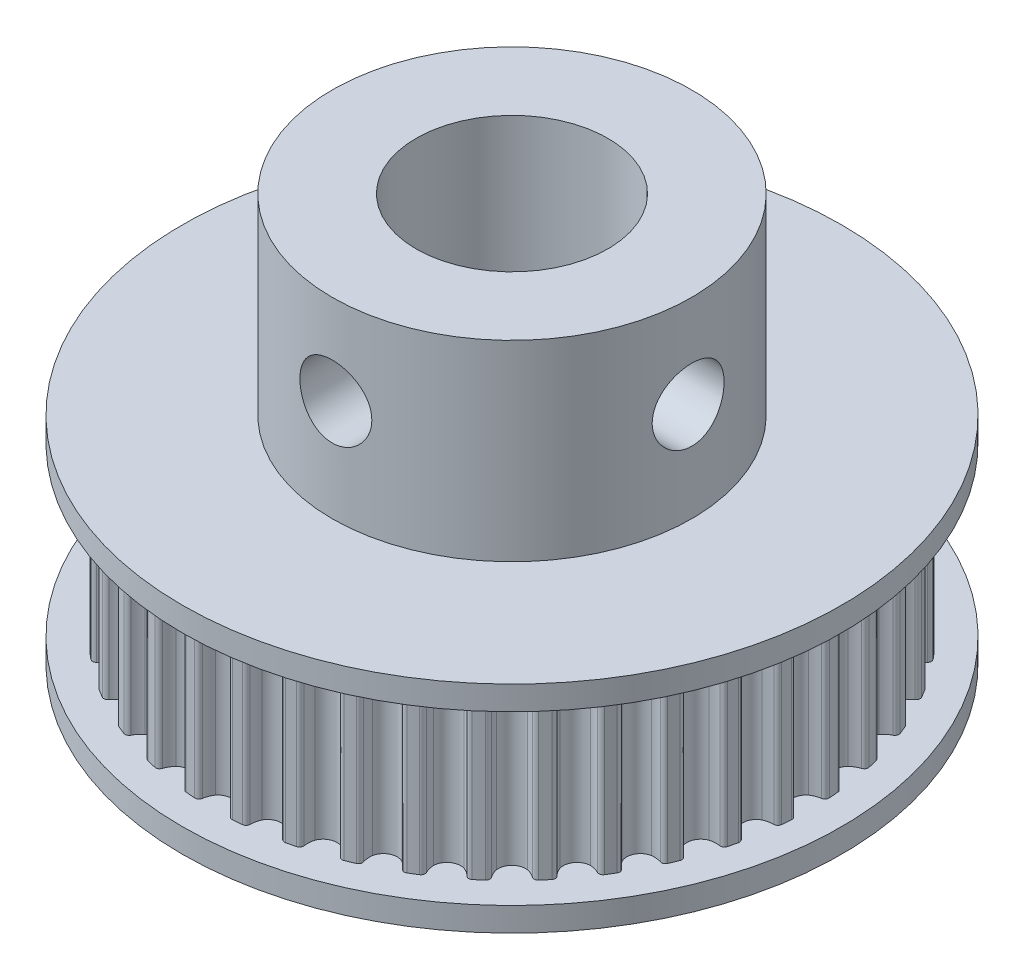
SolidWorks part; units mm, degrees
ref_plane "Front Plane" through (0, 0, 0) normal (0, 0, 1) x (1, 0, 0)
ref_plane "Top Plane" through (0, 0, 0) normal (0, 1, 0) x (1, 0, 0)
ref_plane "Right Plane" through (0, 0, 0) normal (1, 0, 0) x (0, 0, -1)
sketch "Sketch1" plane through (0, 0, 0) normal (0, 1, 0) x (1, 0, 0)
  circle A0 centre (0, 0) radius 12.4784
  dimension "D1" = 24.9568
extrude "Boss-Extrude1" add sketch "Sketch1" along normal blind 7
sketch "Sketch2" plane through (0, 7, 0) normal (0, 1, 0) x (1, 0, 0)
  line L0 (0, 0) -> (0, 12.4784) construction
  line L1 (0, 12.4784) -> (-0.4, 12.4784) construction
  line L2 (0, 12.4784) -> (0.4, 12.4784) construction
  circle A0 centre (0, 0) radius 12.4784
  circle A1 centre (0, 0) radius 12.2734 construction
  circle A2 centre (0, 0) radius 11.7184 construction
  arc A4 (-0.6199, 12.463) -> (-0.4536, 11.92) centre (0.4, 12.4784) ccw
  arc A5 (-0.4536, 11.92) -> (0.4536, 11.92) centre (0, 12.2734) ccw
  arc A6 (0.4536, 11.92) -> (0.6199, 12.463) centre (-0.4, 12.4784) ccw
  dimension "D1" = 24.9568
  dimension "D2" = 23.4368
  dimension "D3" = 24.5468
  dimension "D7" = 2.04
  dimension "D8" = 1.15
  dimension "D4" = 0.4
  dimension "D5" = 0.4
extrude "Cut-Extrude1" cut sketch "Sketch2" against normal blind 10 contours A5 A6 A0 A4 region at (0, 7, -12.1404)
fillet "Fillet1" radius 0.17 2 edges at (0.6199, 3.5, -12.463) (-0.6199, 3.5, -12.463)
ref_axis "Axis2" through (0, 7, 0) along (0, -1, 0)
pattern_circular "CirPattern2" count 40 over 360 about axis through (0, 7, 0) along (0, -1, 0) of "Cut-Extrude1", "Fillet1"
sketch "Sketch3" plane through (0, 7, 0) normal (0, 1, 0) x (1, 0, 0)
  circle A0 centre (0, 0) radius 13.75
  dimension "D1" = 27.5
extrude "Boss-Extrude2" add sketch "Sketch3" along normal blind 1
sketch "Sketch4" plane through (0, 0, 0) normal (0, -1, 0) x (1, 0, 0)
  circle A0 centre (0, 0) radius 13.75
  dimension "D1" = 27.5
extrude "Boss-Extrude3" add sketch "Sketch4" along normal blind 1
sketch "Sketch5" plane through (0, 8, 0) normal (0, 1, 0) x (1, 0, 0)
  circle A0 centre (0, 0) radius 7.5
  circle A1 centre (0, 0) radius 4
  dimension "D1" = 15
  dimension "D2" = 8
extrude "Boss-Extrude4" add sketch "Sketch5" along normal blind 8
sketch "Sketch6" plane through (0, 8, 0) normal (0, 1, 0) x (1, 0, 0)
  circle A0 centre (0, 0) radius 4
  dimension "D1" = 8
extrude "Cut-Extrude2" cut sketch "Sketch6" against normal through all
ref_plane "Plane1" through (7.5, 0, 0) normal (1, 0, 0) x (0, 0, -1)
sketch "Sketch7" plane through (7.5, 0, 0) normal (1, 0, 0) x (0, 0, -1)
  circle A0 centre (0, 12.1224) radius 1.5
  dimension "D1" = 3
extrude "Cut-Extrude3" cut sketch "Sketch7" against normal up to next
ref_plane "Plane2" through (0, 0, 7.5) normal (0, 0, 1) x (1, 0, 0)
sketch "Sketch8" plane through (0, 0, 7.5) normal (0, 0, 1) x (1, 0, 0)
  circle A0 centre (0, 12.2394) radius 1.5
  dimension "D1" = 3
extrude "Cut-Extrude4" cut sketch "Sketch8" against normal up to next
equation "\"GD\"= 0.76mm"
equation "\"SBD\"= 2mm"
equation "\"NT\"= 40"
equation "\"PD\"= ( \"SBD\" * \"NT\" ) / 3.14159"
equation "\"U\"= 0.254mm"
equation "\"OD\"= \"PD\" - ( 2 * \"U\" )"
equation "\"RD\"= \"OD\" - ( 2 * \"GD\" )"
equation "\"R3\"= 0.555mm"
equation "\"R2\"= 1mm"
equation "\"R1\"= 0.15mm"
equation "\"DT\"= 0.02mm"
equation "\"b\"= 0.4mm"
equation "\"D1@Sketch1\"= \"OD\""
equation "\"D1@Sketch2\"= \"OD\""
equation "\"D3@Sketch2\"= \"RD\" + \"R3\" * 2"
equation "\"D2@Sketch2\"= \"RD\""
equation "\"D4@Sketch2\"= \"b\""
equation "\"D5@Sketch2\"= \"b\""
equation "\"D7@Sketch2\"= ( \"R2\" + \"DT\" ) * 2"
equation "\"D8@Sketch2\"= ( \"R3\" + \"DT\" ) * 2"
equation "\"D1@Fillet1\"=\"R1\"+\"DT\""
equation "\"D1@CirPattern2\"=\"NT\""
